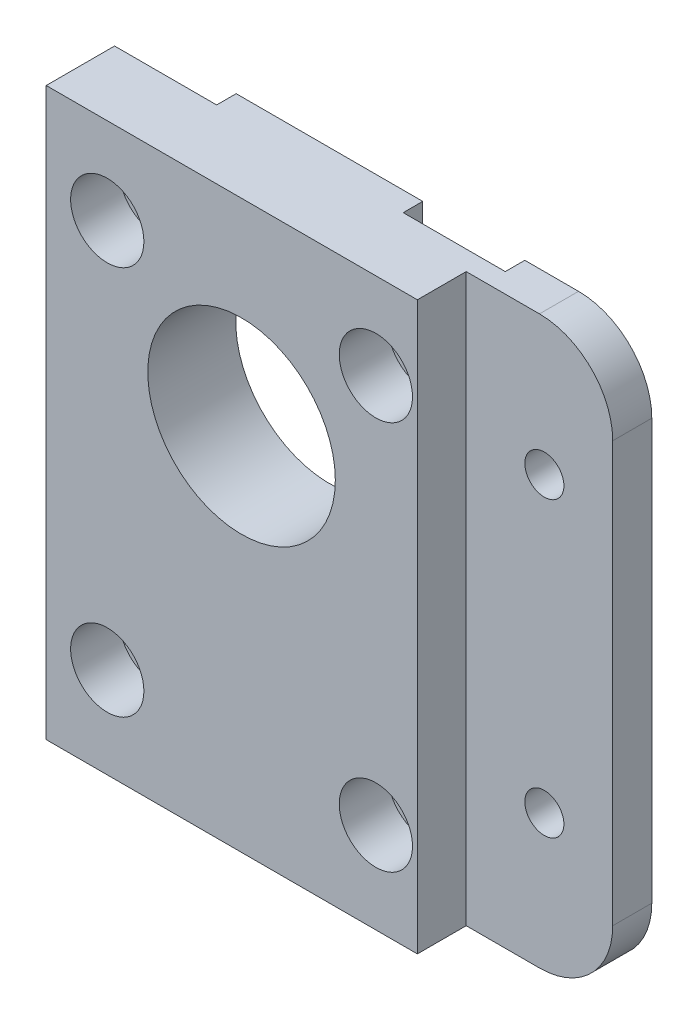
SolidWorks part; units mm, degrees
material "1060 Alloy"
ref_plane "Front Plane" through (0, 0, 0) normal (0, 0, 1) x (1, 0, 0)
ref_plane "Top Plane" through (0, 0, 0) normal (0, 1, 0) x (1, 0, 0)
ref_plane "Right Plane" through (0, 0, 0) normal (1, 0, 0) x (0, 0, -1)
sketch "Sketch1" plane through (0, 0, 0) normal (0, 0, 1) x (1, 0, 0)
  line L0 (-13.75, -19.7) -> (-9.6769, -16.8) construction
  line L3 (20, 29) -> (33, 29)
  line L8 (20, -29) -> (-20, -29)
  line L9 (20, -29) -> (20, 29) construction
  line L10 (33, 29) -> (33, -29)
  line L11 (20, 29) -> (-20, 29)
  line L14 (-20, -29) -> (-20, 29)
  line L15 (20, -29) -> (-20, 29) construction
  line L16 (20, 29) -> (-20, -29) construction
  line L17 (-16.186, -16.2786) -> (-12.1129, -13.3786)
  line L18 (-11.314, -23.1214) -> (-7.2409, -20.2214)
  line L19 (0, -29) -> (0, 29) construction
  line L22 (33, -29) -> (20, -29)
  line L23 (17.2075, -17.3155) -> (20, -21.3647)
  line L24 (9.55, -19.7) -> (9.55, -29)
  line L25 (-9.55, 20.15) -> (-9.55, 29)
  line L26 (-17.2075, 17.7655) -> (-20, 21.8147)
  line L27 (9.55, 20.15) -> (9.55, 29)
  line L28 (17.2075, 17.7655) -> (20, 21.8147)
  line L29 (20, 21.8147) -> (20, 29)
  line L30 (-16.186, -16.2786) -> (-20, -16.2786)
  line L31 (20, -29) -> (20, -21.3647)
  line L32 (-11.314, -29) -> (-11.314, -23.1214)
  circle A18 centre (-13.75, 20.15) radius 4.2
  circle A19 centre (13.75, 20.15) radius 4.2
  circle A20 centre (13.75, -19.7) radius 4.2
  arc A21 (-16.186, -16.2786) -> (-11.314, -23.1214) centre (-13.75, -19.7) ccw
  arc A22 (-7.2409, -20.2214) -> (-12.1129, -13.3786) centre (-9.6769, -16.8) ccw
  circle A23 centre (0, 8.8) radius 9.6
  circle A24 centre (-5.725, -6.1) radius 4.2
  circle A25 centre (5.725, -6.1) radius 4.2
  point P0 (0, 0)
  point P14 (-6.2555, -14.364)
  point P31 (-11.7135, -18.25)
  point P37 (5.725, -10.3)
  point P43 (20, 29)
  point P46 (-20, 29)
  dimension "D1" = 58
  dimension "D2" = 40
  dimension "D3" = 12.2
  dimension "D4" = 8.4
  dimension "D5" = 8.4
  dimension "D6" = 19.2
  dimension "D7" = 9.3
  dimension "D8" = 27.5
  dimension "D9" = 39.85
  dimension "D10" = 5
  dimension "D12" = 20.2
  dimension "D13" = 11.45
  dimension "D14" = 22.9
  dimension "D15" = 13
extrude "Boss-Extrude1" add sketch "Sketch1" along normal blind 2 contours L11 L14 L8 L9 A25 A24 A23 A22 L18 A21 L17 A20 A19 A18 region at (9.5102, -0.5461, 0)
sketch "Sketch4" plane through (0, 0, 2) normal (0, 0, 1) x (1, 0, 0)
  line L0 (0, -29) -> (0, 29) construction
  line L6 (33, -29) -> (20, -29) construction
  line L8 (-20, -29) -> (33, -29)
  line L11 (33, -29) -> (33, 29)
  line L12 (-20, 29) -> (-20, -29)
  line L13 (-20, -16.2786) -> (-20, 21.8147) construction
  line L14 (-20, 29) -> (33, 29)
  line L15 (20, 29) -> (33, 29) construction
  line L16 (33, 29) -> (33, -29) construction
  circle A2 centre (13.75, -19.7) radius 2
  circle A3 centre (-13.75, 20.15) radius 2
  circle A4 centre (13.75, 20.15) radius 2
  circle A10 centre (-13.75, -19.7) radius 2
  circle A11 centre (0, 8.8) radius 9.6
  circle A12 centre (0, 8.8) radius 9.6 construction
  dimension "D1" = 4
extrude "Boss-Extrude3" add sketch "Sketch4" along normal blind 2
sketch "Sketch5" plane through (0, 0, 4) normal (0, 0, 1) x (1, 0, 0)
  line L0 (-20, 0) -> (33, 0) construction
  line L3 (-20, 29) -> (-20, -29) construction
  line L4 (33, -29) -> (33, 29) construction
  circle A0 centre (26, 15) radius 2
  circle A1 centre (26, -15) radius 2
  dimension "D1" = 4
  dimension "D2" = 15
  dimension "D3" = 46
extrude "Cut-Extrude1" cut sketch "Sketch5" against normal blind 4
ref_plane "Plane1" through (0, 0, 0) normal (0, 0, -1) x (-1, 0, 0)
sketch "Sketch6" plane through (0, 0, 4) normal (0, 0, 1) x (1, 0, 0)
  line L0 (18, 29) -> (18, -29)
  line L1 (33, 29) -> (-20, 29) construction
  line L2 (-20, -29) -> (33, -29) construction
  line L3 (33, -29) -> (33, 29) construction
  circle A52 centre (-13.75, 20.15) radius 3.75
  circle A53 centre (13.75, 20.15) radius 3.75
  circle A54 centre (26, 15) radius 2
  circle A55 centre (13.75, -19.7) radius 3.75
  circle A56 centre (-13.75, -19.7) radius 3.75
  circle A57 centre (26, -15) radius 2
  circle A59 centre (26, 15) radius 2 construction
  circle A60 centre (26, -15) radius 2 construction
  line M5 (-20, 29) -> (-20, -29)
  line M6 (-20, -29) -> (33, -29)
  line M7 (33, -29) -> (33, 29)
  line M8 (33, 29) -> (-20, 29)
  circle M11 centre (0, 8.8) radius 9.6
  dimension "D1" = 7.5
  dimension "D2" = 15
extrude "Boss-Extrude4" add sketch "Sketch6" along normal blind 5 contours A57 A56 A55 A54 A53 A52 M8 M5 M6 M7 M11 region at (-1.2683, -1.4891, 4)
sketch "Sketch7" plane through (0, 0, 4) normal (0, 0, 1) x (1, 0, 0)
  line L0 (33, -29) -> (33, 29) construction
  line L1 (25.5, 29) -> (33, 29)
  line L2 (33, 29) -> (33, 21.5)
  line L3 (-20, 0) -> (33, 0) construction
  line L4 (-20, 29) -> (-20, -29) construction
  line L5 (33, -29) -> (33, -21.5)
  line L6 (25.5, -29) -> (33, -29)
  arc A0 (33, 21.5) -> (25.5, 29) centre (25.5, 21.5) ccw
  arc A1 (33, -21.5) -> (25.5, -29) centre (25.5, -21.5) cw
  dimension "D1" = 15
extrude "Cut-Extrude2" cut sketch "Sketch7" against normal through all
